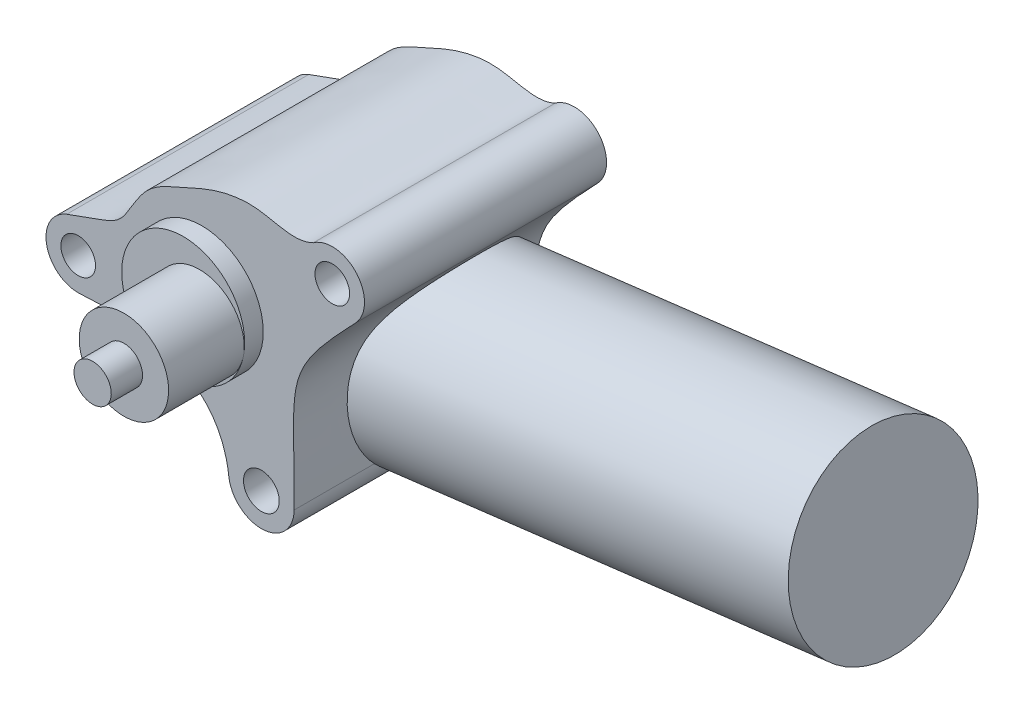
SolidWorks part; units mm, degrees
ref_plane "Front Plane" through (0, 0, 0) normal (0, 0, 1) x (1, 0, 0)
ref_plane "Top Plane" through (0, 0, 0) normal (0, 1, 0) x (1, 0, 0)
ref_plane "Right Plane" through (0, 0, 0) normal (1, 0, 0) x (0, 0, -1)
sketch "Sketch1" plane through (0, 0, 0) normal (1, 0, 0) x (0, 0, -1)
  line L0 (0, 0) -> (0, 5)
  line L1 (0, 5) -> (8.4, 5)
  line L2 (8.4, 5) -> (8.4, 12)
  line L3 (8.4, 12) -> (28.7, 12)
  line L4 (28.7, 12) -> (28.7, 0)
  line L5 (28.7, 0) -> (0, 0)
  dimension "D1" = 5
  dimension "D2" = 8.4
  dimension "D3" = 28.7
  dimension "D4" = 12
revolve "Revolve1" add sketch "Sketch1" angle 360 about L5
sketch "Sketch2" plane through (0, 0, -28.7) normal (0, 0, -1) x (-1, 0, 0)
  circle A0 centre (4.39, 0.99) radius 16.5002
  circle A1 centre (0, 0) radius 12 construction
  dimension "D1" = 4.39
  dimension "D2" = 0.99
extrude "Boss-Extrude1" add sketch "Sketch2" along normal blind 5
ref_axis "Axis1" through (0, 0, -8.4) along (0, 0, -1)
ref_axis "Axis2" through (-4.39, 0.99, -33.7) along (0, 0, 1)
sketch "Sketch3" plane through (0, 0, -33.7) normal (0, 0, -1) x (-1, 0, 0)
  line L0 (4.39, 0.99) -> (48.6074, 0.99) construction
  line L1 (37.58, -6.0648) -> (4.39, 0.99) construction
  circle A0 centre (37.58, -6.0648) radius 4.65
  circle A1 centre (-11.61, -36.17) radius 4.8
  circle A2 centre (-30.65, 21.5) radius 4.65
  circle A3 centre (-30.65, 21.5) radius 8.65
  circle A4 centre (37.58, -6.0648) radius 8.65
  circle A5 centre (-11.61, -36.17) radius 8.8
  spline S0 degree 3 poles (36.9554, -14.6922) (22.1954, -13.6236) (-0.238, -15.0657) (-2.8716, -37.2093) knots 0 0 0 0 1 1 1 1
  spline S1 degree 3 poles (-36.8927, 15.5125) (-16.66, -5.5827) (-20.6384, -4.7861) (-20.4098, -36.234) knots 0 0 0 0 1 1 1 1
  spline S2 degree 3 poles (40.6648, 2.0165) (29.809, 6.1604) (26.3225, 5.8902) (19.6422, 19.806) (11.0598, 22.9915) (1.6689, 27.5301) (-10.6116, 30.6643) (-20.5379, 25.9614) (-25.5482, 28.4853) knots 0 0 0 0 0.235358 0.373961 0.518248 0.593954 0.794428 1 1 1 1
  circle M1 centre (4.39, 0.99) radius 16.5002
  dimension "D1" = 9.3
  dimension "D2" = 9.6
  dimension "D3" = 9.3
  dimension "D4" = 33.19
  dimension "D5" = 20.51
  dimension "D6" = 35.04
  dimension "D7" = 12
  dimension "D8" = 16
  dimension "D9" = 37.16
  dimension "D11" = 4.39
  dimension "D12" = 0.99
  dimension "D10" = 4
extrude "Boss-Extrude2" add sketch "Sketch3" along normal blind 65 separate body contours A4 S2 A3 S1 A5 S0 M1 | A3 A2 | A5 A1 | A4 A0 | M1 region at (27.5146, 13.7013, -33.7) region at (22.0291, 25.8791, -33.7) region at (-44.5026, -1.2974, -33.7) region at (11.6411, -27.619, -33.7) region at (-4.39, 0.99, -33.7)
ref_plane "Plane1" through (0, 0, -73.4) normal (0, 0, -1) x (-1, 0, 0)
sketch "Sketch4" plane through (0, 0, -73.4) normal (0, 0, -1) x (-1, 0, 0)
  line L0 (-12.6825, -44.9044) -> (-150.9894, -27.9225)
  line L1 (-150.9894, -27.9225) -> (-144.1647, 27.6601)
  line L2 (-144.1647, 27.6601) -> (-35.7839, 14.3526)
  line L3 (-12.6825, -44.9044) -> (-169.222, -44.9044) construction
  line L4 (-147.577, -0.1312) -> (104.2516, -31.0518) construction
  arc A0 (-20.4098, -36.234) -> (-2.8716, -37.2093) centre (-11.61, -36.17) ccw construction
  arc A2 (36.9554, -14.6922) -> (40.6648, 2.0165) centre (37.58, -6.0648) ccw construction
  arc A3 (-20.4098, -36.234) -> (-12.6825, -44.9044) centre (-11.61, -36.17) ccw
  spline S0 degree 3 poles (-1219.9157, 1627) (940.9923, -1580.5216) (-786.2446, 1667.7627) (586.3687, -1940.1211) knots -2.633888 -2.633888 -2.633888 -2.633888 3.631074 3.631074 3.631074 3.631074 only from (-36.8927, 15.5125) to (-20.4098, -36.234) construction
  spline S1 degree 3 poles (-35.7839, 14.3526) (-16.8072, -5.5642) (-20.6342, -5.3737) (-20.4098, -36.234) knots 0.018684 0.018684 0.018684 0.018684 1 1 1 1
  dimension "D2" = 184.5
  dimension "D1" = 7
  dimension "D3" = 56
sketch "Sketch6" plane through (0, 0, -73.4) normal (0, 0, -1) x (-1, 0, 0)
  line L0 (-135.9055, 20.1742) -> (-141.0056, -21.3629)
  line L1 (-141.0056, -21.3629) -> (-100.8899, -21.3629) construction
  arc A0 (36.9554, -14.6922) -> (40.6648, 2.0165) centre (37.58, -6.0648) ccw construction
  point P6 (46.0244, -7.9394)
  dimension "D1" = 83
  dimension "D2" = 184
ref_plane "Plane3" through (136.3273, 16.7389, 0) normal (0.9925, 0.1219, 0) x (0.1219, -0.9925, 0)
sketch "Sketch7" plane through (136.3273, 16.7389, 0) normal (0.9925, 0.1219, 0) x (0.1219, -0.9925, 0)
  line L0 (38.4512, 98.7) -> (-10.9007, 98.7) construction
  line L4 (46.1153, 33.7) -> (46.1153, 98.7) construction
  circle A0 centre (20.8153, 73.4) radius 25.3
  dimension "D1" = 50.6
extrude "Boss-Extrude4" add sketch "Sketch7" against normal up to next
